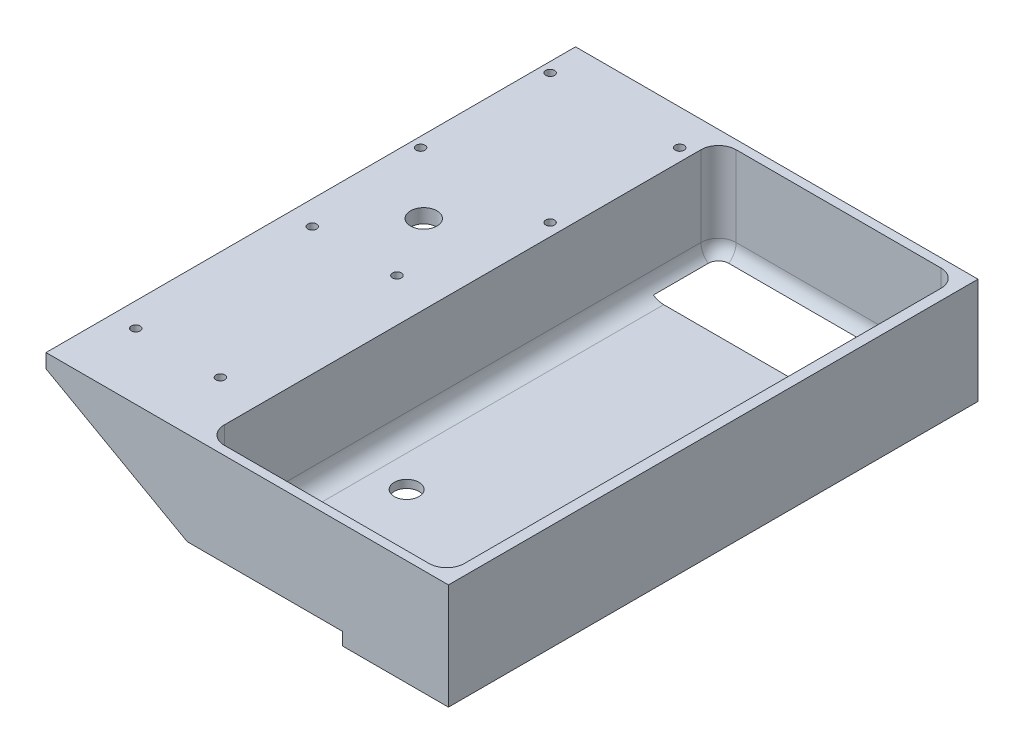
SolidWorks part; units mm, degrees
ref_plane "Front Plane" through (0, 0, 0) normal (0, 0, 1) x (1, 0, 0)
ref_plane "Top Plane" through (0, 0, 0) normal (0, 1, 0) x (1, 0, 0)
ref_plane "Right Plane" through (0, 0, 0) normal (1, 0, 0) x (0, 0, -1)
sketch "Sketch1" plane through (0, 0, 0) normal (0, 1, 0) x (1, 0, 0)
  line L1 (-37, 75) -> (37, 75)
  line L2 (-37, 75) -> (-37, -75)
  line L3 (-37, -75) -> (37, -75)
  line L4 (37, 75) -> (37, -75)
  line L5 (-37, 75) -> (37, -75) construction
  line L6 (-37, -75) -> (37, 75) construction
  point P0 (0, 0)
  dimension "D1" = 74
  dimension "D2" = 150
extrude "Boss-Extrude1" add sketch "Sketch1" against normal blind 30
sketch "Sketch2" plane through (0, 0, 0) normal (0, 1, 0) x (1, 0, 0)
  line L1 (-34, 72.5) -> (34, 72.5)
  line L2 (-34, 72.5) -> (-34, -72.5)
  line L3 (-34, -72.5) -> (34, -72.5)
  line L4 (34, 72.5) -> (34, -72.5)
  line L5 (-34, 72.5) -> (34, -72.5) construction
  line L6 (-34, -72.5) -> (34, 72.5) construction
  point P0 (0, 0)
  dimension "D1" = 145
  dimension "D2" = 68
extrude "Cut-Extrude1" cut sketch "Sketch2" against normal blind 27.75
sketch "Sketch5" plane through (0, -27.75, 0) normal (0, 1, 0) x (1, 0, 0)
  line L0 (34, -72.5) -> (34, 72.5) construction
  line L1 (-34, -72.5) -> (34, -72.5) construction
  circle A0 centre (24.1621, 37.001) radius 3.5
  circle A1 centre (24, -62.5) radius 3.5
  circle A2 centre (-20.0997, -29.7518) radius 3.5
  point P0 (24.1621, 37.001)
  point P1 (24, -62.5)
  dimension "D5" = 7
  dimension "D6" = 7
  dimension "D3" = 7
  dimension "D1" = 10
  dimension "D2" = 10
extrude "Cut-Extrude2" cut sketch "Sketch5" against normal blind 10
fillet "Fillet1" radius 5 8 edges at (0, -27.75, 72.5) (0, -27.75, -72.5) (34, -27.75, 0) (-34, -13.875, 72.5) (34, -13.875, 72.5) (34, -13.875, -72.5) (-34, -13.875, -72.5) (-34, -27.75, 0)
sketch "Sketch6" plane through (-37, 0, 0) normal (-1, 0, 0) x (0, 0, 1)
  line L0 (75, -30) -> (75, 0) construction
  line L1 (-75, 0) -> (75, 0)
  line L2 (-75, 0) -> (-75, -4)
  line L3 (-75, -4) -> (75, -4)
  line L4 (75, 0) -> (75, -4)
  dimension "D1" = 4
extrude "Boss-Extrude2" add sketch "Sketch6" along normal blind 40
sketch "Sketch7" plane through (0, 0, 0) normal (0, 0, 1) x (1, 0, 0)
  line L0 (-77, -4) -> (-37, -30)
rib "Rib1" sketch "Sketch7" sketch "Sketch7" thickness 5 extrusion direction parallel to sketch draft on no parameters "D1"=5
fillet "Fillet2" radius 3 6 edges at (-57, -4, -2.5) (-37, -17, -2.5) (-37, -17, 2.5) (-57, -4, 2.5) (-37, -4, -38.75) (-37, -4, 38.75)
sketch "Sketch9" plane through (0, 0, 0) normal (0, 1, 0) x (1, 0, 0)
  circle A0 centre (-74.2, 65) radius 1.25
  circle A1 centre (-74.2, 28.3) radius 1.25
  circle A2 centre (-37.5, 65) radius 1.25
  circle A3 centre (-37.5, 28.3) radius 1.25
  dimension "D1" = 2.5
extrude "Cut-Extrude3" cut sketch "Sketch9" against normal blind 7
sketch "Sketch10" plane through (0, 0, 0) normal (0, 1, 0) x (1, 0, 0)
  circle A0 centre (-56.4005, 11.4013) radius 3.75
  dimension "D1" = 7.5
extrude "Cut-Extrude4" cut sketch "Sketch10" against normal blind 7
sketch "Sketch11" plane through (-37, 0, 0) normal (-1, 0, 0) x (0, 0, 1)
  line L1 (77.2213, -30) -> (52.0963, -30)
  line L2 (77.2213, -30) -> (77.2213, -26.4037)
  line L3 (77.2213, -26.4037) -> (52.0963, -26.4037)
  line L4 (52.0963, -30) -> (52.0963, -26.4037)
  line L5 (-76.8789, -30) -> (-51.9788, -30)
  line L6 (-76.8789, -30) -> (-76.8789, -26.821)
  line L7 (-76.8789, -26.821) -> (-51.9788, -26.821)
  line L8 (-51.9788, -30) -> (-51.9788, -26.821)
extrude "Cut-Extrude5" cut sketch "Sketch11" against normal blind 44
sketch "Sketch12" plane through (0, 0, 0) normal (0, 1, 0) x (1, 0, 0)
  circle A0 centre (-70.2076, -6.3805) radius 1.25
  circle A1 centre (-46.2076, -6.3805) radius 1.25
  circle A2 centre (-46.2076, -56.3805) radius 1.25
  circle A3 centre (-70.2076, -56.3805) radius 1.25
  dimension "D1" = 2.5
  dimension "D2" = 24
  dimension "D3" = 50
extrude "Cut-Extrude6" cut sketch "Sketch12" against normal blind 10
sketch "Sketch15" plane through (0, 0, 75) normal (0, 0, 1) x (1, 0, 0)
  line L0 (-37, -26.4037) -> (-77, -4)
rib "Rib10" sketch "Sketch15" sketch "Sketch15" thickness 5 extrusion direction parallel to sketch draft on no parameters "D1"=5
fillet "Fillet3" radius 5 3 edges at (-58.5, -4, 70) (-37.8787, -4.8787, 70) (-37, -16.7018, 70)
sketch "Sketch17" plane through (0, 0, -75) normal (0, 0, -1) x (-1, 0, 0)
  line L0 (37, -26.821) -> (77, -4)
rib "Rib15" sketch "Sketch17" sketch "Sketch17" thickness 3 extrusion direction parallel to sketch draft on no parameters "D1"=3
fillet "Fillet4" radius 5 3 edges at (-37, -16.9105, -72) (-37.8787, -4.8787, -72) (-58.5, -4, -72)
